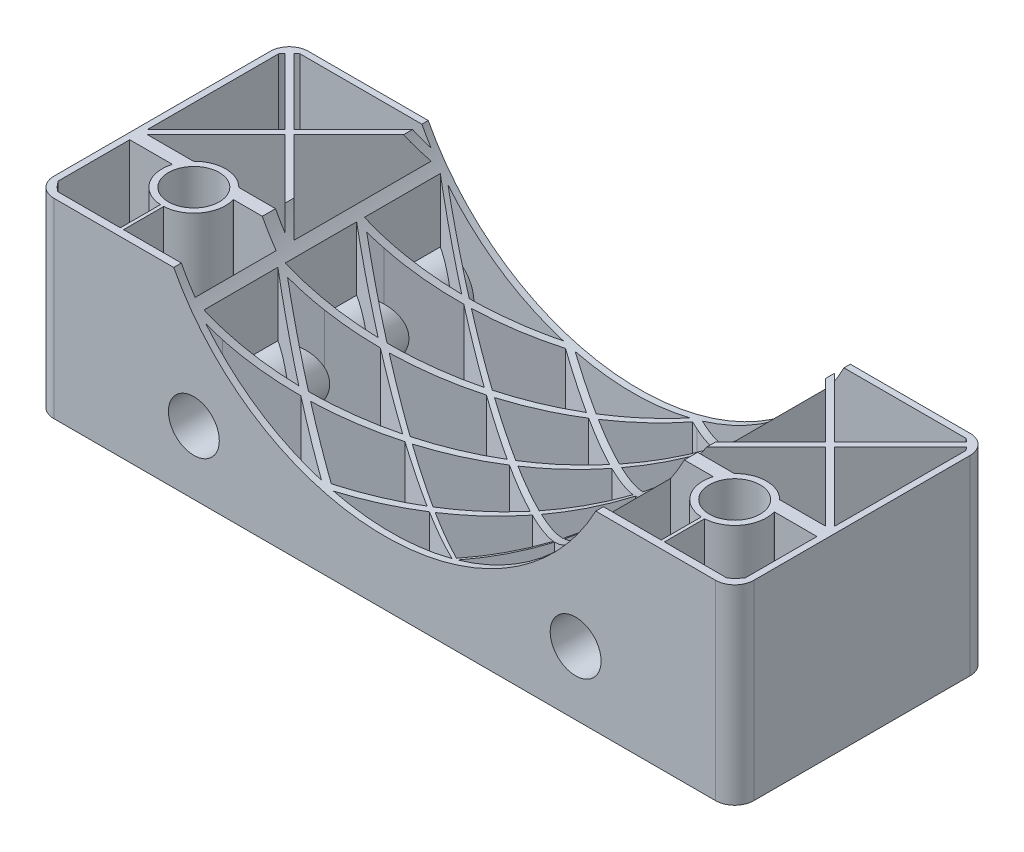
SolidWorks part; units mm, degrees
ref_plane "Front Plane" through (0, 0, 0) normal (0, 0, 1) x (1, 0, 0)
ref_plane "Top Plane" through (0, 0, 0) normal (0, 1, 0) x (1, 0, 0)
ref_plane "Right Plane" through (0, 0, 0) normal (1, 0, 0) x (0, 0, -1)
other "Center of Mass"
ref_plane "Plane1" through (55, 0, 0) normal (1, 0, 0) x (0, 0, -1)
ref_plane "Plane2" through (0, 0, -20) normal (0, 0, 1) x (1, 0, 0)
sketch "Sketch1" plane through (0, 0, 0) normal (0, 1, 0) x (1, 0, 0)
  line L1 (0, 0) -> (110, 0)
  line L2 (0, 0) -> (0, 40)
  line L3 (0, 40) -> (110, 40)
  line L4 (110, 0) -> (110, 40)
  dimension "D1" = 110
  dimension "D2" = 40
extrude "Boss-Extrude1" add sketch "Sketch1" along normal blind 30
sketch "Sketch2" plane through (0, 0, 0) normal (0, 0, 1) x (1, 0, 0)
  line L0 (55, 0) -> (55, 10) construction
  line L1 (0, 0) -> (110, 0) construction
  line L2 (55, 10) -> (55, 47.5) construction
  circle A0 centre (55, 47.5) radius 37.5
  point P5 (55, 0)
  dimension "D2" = 75
  dimension "D1" = 10
extrude "Cut-Extrude1" cut sketch "Sketch2" against normal blind 40
sketch "Sketch3" plane through (0, 0, 0) normal (0, -1, 0) x (1, 0, 0)
  line L0 (110, -20) -> (85, -20) construction
  line L2 (110, 0) -> (110, -40) construction
  line L3 (0, -40) -> (0, 0) construction
  line L4 (0, -20) -> (25, -20) construction
  line L5 (0, -12.5) -> (12.5, -12.5) construction
  line L6 (12.5, -12.5) -> (12.5, 0) construction
  line L7 (0, 0) -> (110, 0) construction
  circle A0 centre (12.5, -12.5) radius 4
  dimension "D5" = 8
  dimension "D1" = 25
  dimension "D2" = 25
  dimension "D3" = 12.5
  dimension "D4" = 12.5
extrude "Cut-Extrude3" cut sketch "Sketch3" against normal blind 30
mirror "Mirror1" about plane through (55, 0, 0) normal (1, 0, 0) of "Cut-Extrude3"
sketch "Sketch7" plane through (0, 0, 0) normal (0, 0, 1) x (1, 0, 0)
  line L2 (55, -16.5) -> (55, 16.5) construction
  circle A2 centre (25, 10) radius 4
  circle A4 centre (85, 10) radius 4
  dimension "D1" = 60
extrude "Cut-Extrude6" cut sketch "Sketch7" against normal blind 40
sketch "Sketch9" plane through (0, 0, 0) normal (0, -1, 0) x (1, 0, 0)
  line L0 (12.5, -12.5) -> (12.5, 0) construction
  line L1 (0, 0) -> (110, 0) construction
  line L2 (12.5, 0) -> (12.5, -40) construction
  line L3 (110, -40) -> (0, -40) construction
  line L4 (1.7071, -39) -> (12.5, -28.2071)
  line L5 (25, 0) -> (25, -40) construction
  line L6 (1.7071, -39) -> (21.7913, -39)
  line L7 (0, -40) -> (0, 0) construction
  line L8 (25, -40) -> (0, -15) construction
  line L9 (0, -15) -> (25, -15) construction
  line L10 (25, -15) -> (0, -40) construction
  line L11 (12.5, -28.2071) -> (23.2929, -39)
  line L12 (23.2929, -39) -> (21.7913, -39)
  line L13 (1, -16.7071) -> (11.7929, -27.5)
  line L14 (1, -38.2929) -> (1, -36.7913)
  line L15 (11.7929, -27.5) -> (1, -38.2929)
  line L16 (1, -16.7071) -> (1, -36.7913)
  line L17 (23.2929, -16) -> (12.5, -26.7929)
  line L19 (12.5, -26.7929) -> (1.7071, -16)
  line L21 (24, -38.2929) -> (13.2071, -27.5)
  line L22 (24, -16.7071) -> (24, -18.2087)
  line L23 (13.2071, -27.5) -> (24, -16.7071)
  line L24 (24, -38.2929) -> (24, -18.2087)
  line L26 (1.7071, -16) -> (8.9293, -16)
  line L27 (23.2929, -16) -> (16.3426, -16) [skipped]
  line L28 (1.7071, -16) -> (3.2087, -16) [skipped]
  line L29 (16.0707, -16) -> (23.2929, -16)
  line L31 (12.25, -1.1996) -> (1, -1.1996)
  line L32 (1, -1.1996) -> (1, -13.9249)
  line L33 (12.25, -1.1996) -> (12.25, -7.5063)
  line L34 (1, -13.9249) -> (7.7073, -13.9249)
  line L35 (7.7073, -13.9249) -> (7.6892, -13.8624)
  line L36 (17.2927, -13.9249) -> (17.3108, -13.8624)
  line L37 (12.75, -1.1996) -> (12.75, -7.5063)
  line L38 (24, -13.9249) -> (17.2927, -13.9249)
  line L39 (24, -1.1996) -> (24, -13.9249)
  line L40 (12.75, -1.1996) -> (24, -1.1996)
  line L41 (55, -16.5) -> (55, 16.5) construction
  line L42 (85, -15) -> (110, -40) construction
  line L43 (110, -15) -> (85, -15) construction
  line L44 (85, -40) -> (110, -15) construction
  line L45 (85, 0) -> (85, -40) construction
  line L46 (97.5, 0) -> (97.5, -40) construction
  line L47 (97.5, -12.5) -> (97.5, 0) construction
  line L48 (97.25, -1.1996) -> (86, -1.1996)
  line L49 (86, -1.1996) -> (86, -13.9249)
  line L50 (86, -13.9249) -> (92.7073, -13.9249)
  line L51 (97.25, -1.1996) -> (97.25, -7.5063)
  line L52 (92.7073, -13.9249) -> (92.6892, -13.8624)
  line L53 (102.2927, -13.9249) -> (102.3108, -13.8624)
  line L54 (109, -13.9249) -> (102.2927, -13.9249)
  line L55 (97.75, -1.1996) -> (97.75, -7.5063)
  line L56 (109, -1.1996) -> (109, -13.9249)
  line L57 (97.75, -1.1996) -> (109, -1.1996)
  line L58 (93.9293, -16) -> (86.7071, -16)
  line L59 (108.2929, -16) -> (101.0707, -16)
  line L60 (86, -38.2929) -> (86, -18.2087)
  line L61 (96.7929, -27.5) -> (86, -16.7071)
  line L62 (86, -16.7071) -> (86, -18.2087)
  line L63 (86, -38.2929) -> (96.7929, -27.5)
  line L64 (97.5, -26.7929) -> (108.2929, -16)
  line L65 (86.7071, -16) -> (97.5, -26.7929)
  line L66 (109, -16.7071) -> (109, -36.7913)
  line L67 (98.2071, -27.5) -> (109, -38.2929)
  line L68 (109, -38.2929) -> (109, -36.7913)
  line L69 (109, -16.7071) -> (98.2071, -27.5)
  line L70 (86.7071, -39) -> (88.2087, -39)
  line L71 (97.5, -28.2071) -> (86.7071, -39)
  line L72 (108.2929, -39) -> (88.2087, -39)
  line L73 (108.2929, -39) -> (97.5, -28.2071)
  circle A1 centre (12.5, -12.5) radius 4 construction
  arc A3 (8.9293, -16) -> (16.0707, -16) centre (12.5, -12.5) ccw
  arc A5 (12.25, -7.5063) -> (7.6892, -13.8624) centre (12.5, -12.5) ccw
  arc A6 (12.75, -7.5063) -> (17.3108, -13.8624) centre (12.5, -12.5) cw
  arc A7 (97.25, -7.5063) -> (92.6892, -13.8624) centre (97.5, -12.5) ccw
  arc A8 (97.75, -7.5063) -> (102.3108, -13.8624) centre (97.5, -12.5) cw
  arc A9 (101.0707, -16) -> (93.9293, -16) centre (97.5, -12.5) cw
  point P18 (12.5, -27.5)
  point P36 (12.5, -27.5)
  point P39 (12.5, -16.5)
  point P40 (10.5635, -16)
  point P41 (14.4365, -16)
  point P50 (8.9293, -16)
  point P52 (12.25, -7.5063)
  point P53 (7.7073, -13.9249)
  point P98 (102.2927, -13.9249)
  point P99 (97.75, -7.5063)
  point P100 (101.0707, -16)
  point P101 (95.5635, -16)
  point P102 (99.4365, -16)
  point P103 (97.5, -16.5)
  point P104 (97.5, -27.5)
  dimension "D5" = 0.5
  dimension "D1" = 12.5
  dimension "D2" = 1
  dimension "D3" = 0.5
  dimension "D4" = 4
extrude "Cut-Extrude7" cut sketch "Sketch9" against normal blind 30
sketch "Sketch11" plane through (0, 0, 0) normal (0, -1, 0) x (1, 0, 0)
  line L0 (25, -1) -> (25, -39) construction
  line L1 (25, -39) -> (85, -39) construction
  line L2 (85, -39) -> (85, -1) construction
  line L3 (85, -1) -> (25, -1) construction
  line L4 (0, 0) -> (110, 0) construction
  line L5 (24, -13.9249) -> (24, -1.1996) construction
  line L6 (110, -40) -> (0, -40) construction
  line L7 (86, -16.7071) -> (86, -38.2929) construction
  line L8 (55, -1) -> (55, -39) construction
  line L9 (25, -20) -> (54, -20) construction
  line L10 (85, -1) -> (65, -1)
  line L11 (65, -1) -> (45, -1)
  line L12 (45, -1) -> (25, -1)
  line L13 (25, -1) -> (25, -13.6)
  line L14 (25, -13.6) -> (25, -26.2)
  line L15 (25, -26.2) -> (25, -39)
  line L16 (85, -39) -> (65, -39)
  line L17 (45, -39) -> (25, -39)
  line L18 (85, -39) -> (25, -39) construction
  line L19 (65, -39) -> (45, -39)
  line L20 (25, -13.8) -> (25, -1)
  line L21 (85, -26.2) -> (85, -39)
  line L22 (85, -1) -> (85, -13.6)
  line L23 (85, -13.6) -> (85, -26.2)
  line L24 (25, -13.8) -> (45, -1) construction
  line L25 (25, -26.2) -> (65, -1) construction
  line L26 (25, -39) -> (85, -1) construction
  line L27 (45, -39) -> (85, -13.6) construction
  line L28 (65, -39) -> (85, -26.2) construction
  line L29 (85, -13.6) -> (65, -1) construction
  line L30 (85, -26.2) -> (45, -1) construction
  line L31 (85, -39) -> (25, -1) construction
  line L32 (65, -39) -> (25, -13.8) construction
  line L33 (25.86, -2.1365) -> (81.8164, -37.5756)
  line L34 (25.9456, -2.1907) -> (25, -1.5918)
  line L35 (81.8164, -37.5756) -> (84.0655, -39)
  line L36 (27.2382, -1.8257) -> (83.9174, -37.7225)
  line L37 (27.5296, -2.0103) -> (25.86, -1)
  line L38 (83.9174, -37.7225) -> (85, -38.4082)
  line L39 (28.4232, -12.2028) -> (38.2658, -5.9035)
  line L40 (38.2658, -5.9035) -> (45.9276, -1)
  line L41 (37.2659, -5.3562) -> (44.0724, -1)
  line L42 (37.2659, -5.3562) -> (27.9267, -11.3333)
  line L43 (27.9267, -11.3333) -> (25, -13.2064)
  line L44 (47.7229, -3.3064) -> (79.6333, -23.4099)
  line L45 (79.6333, -23.4099) -> (85, -26.791)
  line L46 (47.7229, -3.3064) -> (44.0724, -1)
  line L47 (45.9276, -1) -> (81.2018, -23.2162)
  line L48 (81.2018, -23.2162) -> (85, -25.6083)
  line L49 (63.0254, -2.5395) -> (28.312, -24.7044)
  line L50 (28.312, -24.7044) -> (25, -26.8191)
  line L51 (28.3301, -23.5111) -> (61.7814, -2.7322)
  line L52 (61.7814, -2.7322) -> (64.5701, -1)
  line L53 (63.0254, -2.5395) -> (65.4364, -1)
  line L54 (65.4364, -1) -> (69.4058, -3.4802)
  line L55 (69.4058, -3.4802) -> (85, -13.2239)
  line L56 (64.5701, -1) -> (67.6965, -2.9943)
  line L57 (67.6965, -2.9943) -> (85, -14.0318)
  line L58 (85, -14.0318) -> (81.3497, -16.5102)
  line L59 (67.4512, -38.0249) -> (82.2284, -28.5675)
  line L60 (82.2284, -28.5675) -> (85, -26.791)
  line L61 (67.4512, -38.0249) -> (65.9299, -39)
  line L62 (65.9299, -39) -> (29.5093, -16.0499)
  line L63 (29.5093, -16.0499) -> (25, -13.2064)
  line L64 (28.0981, -16.3428) -> (62.6323, -38.0993)
  line L65 (62.6323, -38.0993) -> (64.062, -39)
  line L66 (28.0981, -16.3428) -> (25, -14.391)
  line L67 (28.3301, -23.5111) -> (25, -25.5796)
  line L68 (29.5859, -36.6874) -> (82.8637, -2.9448)
  line L69 (82.8637, -2.9448) -> (85, -1.5918)
  line L70 (78.5744, -4.4777) -> (29.2621, -36.0047)
  line L71 (29.2621, -36.0047) -> (25, -38.7297)
  line L72 (29.5859, -36.6874) -> (25.9345, -39)
  line L73 (47.1403, -38.2332) -> (81.3497, -16.5102)
  line L74 (80.4967, -15.8673) -> (46.2437, -37.6179)
  line L75 (46.2437, -37.6179) -> (44.0673, -39)
  line L76 (80.4967, -15.8673) -> (85, -13.0077)
  line L77 (78.5744, -4.4777) -> (84.014, -1)
  line L78 (47.1403, -38.2332) -> (45.9276, -39)
  line L79 (66.8535, -37.2201) -> (80.6496, -28.3906)
  line L80 (80.6496, -28.3906) -> (85, -25.6083)
  line L81 (66.8535, -37.2201) -> (64.062, -39)
  line L82 (28.4232, -12.2028) -> (25, -14.391)
  line L83 (25, -26.2) -> (45, -39) construction
  line L84 (26.8548, -27.9807) -> (42.5394, -38.0189)
  line L85 (42.5394, -38.0189) -> (44.0673, -39)
  line L86 (26.8548, -27.9807) -> (25, -26.8191)
  line L87 (27.6269, -27.2876) -> (43.5979, -37.5091)
  line L88 (43.5979, -37.5091) -> (45.9276, -39)
  line L89 (27.6269, -27.2876) -> (25, -25.5796)
  point P18 (35, 7.2209)
  point P35 (82.8637, -2.9448)
  point P37 (29.5859, -36.6874)
  point P38 (29.2621, -36.0047)
  point P39 (28.312, -24.7044)
  point P40 (28.3301, -23.5111)
  point P41 (28.0981, -16.3428)
  point P42 (29.5093, -16.0499)
  point P43 (28.4232, -12.2028)
  point P44 (27.9267, -11.3333)
  point P45 (37.2659, -5.3562)
  point P46 (38.2658, -5.9035)
  point P47 (49.0942, -2.9884)
  point P48 (47.7229, -3.3064)
  point P49 (81.2018, -23.2162)
  point P50 (79.6333, -23.4099)
  point P51 (80.6496, -28.3906)
  point P52 (82.2284, -28.5675)
  point P53 (80.4967, -15.8673)
  point P54 (81.3497, -16.5102)
  point P55 (81.5522, -11.1324)
  point P56 (81.3412, -11.8859)
  point P57 (69.4058, -3.4802)
  point P58 (67.6965, -2.9943)
  point P59 (61.7814, -2.7322)
  point P60 (63.0254, -2.5395)
  point P84 (47.1403, -38.2332)
  point P86 (46.2437, -37.6179)
  point P87 (62.6323, -38.0993)
  point P88 (67.4512, -38.0249)
  point P100 (78.5744, -4.4777)
  point P110 (66.8535, -37.2201)
  point P116 (27.6269, -27.2876)
  point P117 (26.8548, -27.9807)
  point P118 (42.5394, -38.0189)
  point P119 (43.5979, -37.5091)
  dimension "D1" = 1
  dimension "D2" = 1
  dimension "D3" = 1
  dimension "D4" = 1
  dimension "D5" = 1
  dimension "D6" = 0.5
  dimension "D7" = 0.5
  dimension "D8" = 0.5
  dimension "D9" = 0.5
  dimension "D10" = 0.5
  dimension "D11" = 0.5
  dimension "D12" = 0.5
  dimension "D13" = 0.5
  dimension "D14" = 0.5
  dimension "D15" = 0.5
  dimension "D16" = 0.5
  dimension "D17" = 0.5
  dimension "D18" = 0.5
  dimension "D19" = 0.5
  dimension "D20" = 0.5
  dimension "D21" = 0.5
  dimension "D22" = 0.5
  dimension "D23" = 0.5
  dimension "D24" = 0.5
  dimension "D25" = 0.5
  dimension "D26" = 0.5
  dimension "D27" = 0.5
  dimension "D28" = 0.5
  dimension "D29" = 0.5
  dimension "D30" = 0.5
  dimension "D31" = 0.5
  dimension "D32" = 0.5
  dimension "D33" = 0.5
  dimension "D34" = 0.5
  dimension "D35" = 0.5
  dimension "D36" = 0.5
  dimension "D37" = 0.5
  dimension "D38" = 0.5
  dimension "D39" = 0.5
  dimension "D40" = 0.5
  dimension "D41" = 0.5
  dimension "D42" = 0.5
extrude "Cut-Extrude9" cut sketch "Sketch11" against normal blind 30 contours L42 L41 L12 L37 L36 | L43 L42 L33 L34 L20 | L39 L82 L63 L62 L51 L33 | L36 L51 L44 L46 L40 L39 | L51 L52 L11 L47 | L67 L51 L64 L66 L14 | L89 L87 L70 L64 L49 L50 | L84 L86 L15 L71 L70 | L85 L84 L68 L72 L17 | L87 L88 L75 L74 L64 L68 | L70 L33 L49 L62 | L70 L44 L49 L36 | L70 L57 L56 L53 L49 L47 | L70 L77 L10 L54 L55 | L55 L76 L22 L69 L68 | L74 L76 L57 L68 L47 | L74 L44 L68 L36 | L74 L33 L68 L62 | L81 L79 L33 L73 L62 | L73 L78 L19 L65 L64 | L79 L80 L45 L44 L73 L36 | L73 L47 L48 L23 L58 | L60 L59 L36 L38 L21 | L59 L61 L16 L35 L33 region at (74.7607, 0, -2.9568) region at (81.9172, 0, -7.419) region at (65.0368, 0, -7.1857) region at (55.2273, 0, -2.9434) region at (75.1028, 0, -13.5666) region at (82.0015, 0, -19.8799) region at (45.0868, 0, -7.3656) region at (54.9723, 0, -13.6251) region at (65.0173, 0, -19.9708) region at (35.0131, 0, -2.9234) region at (74.9895, 0, -26.2724) region at (44.9596, 0, -20.0172) region at (81.9597, 0, -32.6107) region at (54.9667, 0, -26.3397) region at (35.0085, 0, -13.7155) region at (28.0405, 0, -7.389) region at (35.0517, 0, -26.3591) region at (64.9645, 0, -32.658) region at (44.9944, 0, -32.6738) region at (27.9809, 0, -19.9985) region at (74.9809, 0, -37.0754) region at (28.111, 0, -32.765) region at (54.9851, 0, -37.089) region at (35.0189, 0, -37.0753)
sketch "Sketch12" plane through (0, 0, 0) normal (0, 0, 1) x (1, 0, 0)
  line L0 (55, -16.5) -> (55, 16.5) construction
  circle A0 centre (25, 10) radius 5
  circle A1 centre (85, 10) radius 5
  point P0 (25, 10)
  dimension "D1" = 10
extrude "Boss-Extrude3" add sketch "Sketch12" against normal blind 40
sketch "Sketch15" plane through (0, 0, 0) normal (0, 0, 1) x (1, 0, 0)
  line L0 (55, -16.5) -> (55, 16.5) construction
  circle A0 centre (25, 10) radius 4
  circle A1 centre (85, 10) radius 4
  point P0 (25, 10)
  dimension "D1" = 8
extrude "Cut-Extrude10" cut sketch "Sketch15" against normal blind 40
sketch "Sketch16" plane through (0, 30, 0) normal (0, 1, 0) x (1, 0, 0)
  line L0 (0, 0) -> (6, 0)
  line L1 (0, 0) -> (21.8338, 0) construction
  line L2 (0, 0) -> (0, 6)
  line L3 (0, 40) -> (0, 0) construction
  line L4 (-16.5, 20) -> (16.5, 20) construction
  line L5 (0, 40) -> (0, 34)
  line L6 (0, 40) -> (6, 40)
  line L7 (55, -16.5) -> (55, 16.5) construction
  line L8 (110, 40) -> (104, 40)
  line L9 (110, 40) -> (110, 34)
  line L10 (110, 0) -> (110, 6)
  line L11 (110, 0) -> (104, 0)
  arc A0 (0, 6) -> (6, 0) centre (6, 6) ccw
  arc A1 (0, 34) -> (6, 40) centre (6, 34) cw
  arc A2 (110, 34) -> (104, 40) centre (104, 34) ccw
  arc A3 (110, 6) -> (104, 0) centre (104, 6) cw
  dimension "D1" = 6
  dimension "D2" = 6
extrude "Boss-Extrude4" add sketch "Sketch16" against normal blind 30
fillet "Fillet1" radius 3 4 edges at (0, 15, -40) (110, 15, -40) (110, 15, 0) (0, 15, 0)
